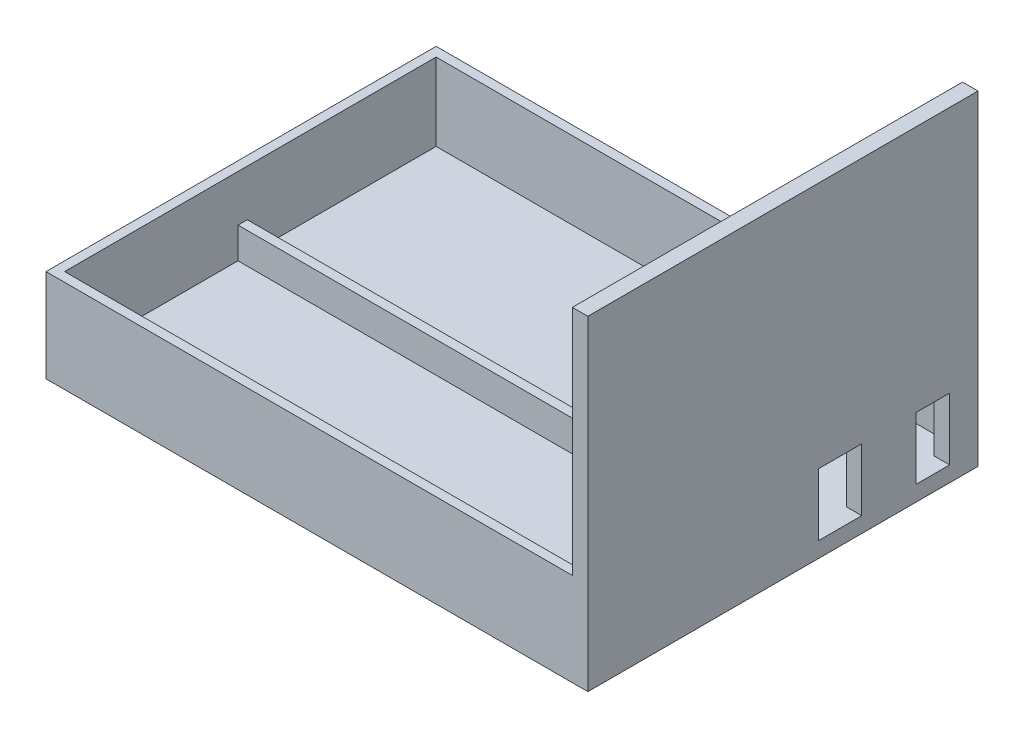
SolidWorks part; units mm, degrees
ref_plane "Płaszczyzna przednia" through (0, 0, 0) normal (0, 0, 1) x (1, 0, 0)
ref_plane "Płaszczyzna górna" through (0, 0, 0) normal (0, 1, 0) x (1, 0, 0)
ref_plane "Płaszczyzna prawa" through (0, 0, 0) normal (1, 0, 0) x (0, 0, -1)
sketch "Szkic1" plane through (0, 0, 0) normal (0, 1, 0) x (1, 0, 0)
  line L1 (-87.5, 63) -> (87.5, 63)
  line L2 (-87.5, 63) -> (-87.5, -63)
  line L3 (-87.5, -63) -> (87.5, -63)
  line L4 (87.5, 63) -> (87.5, -63)
  line L5 (-87.5, 63) -> (87.5, -63) construction
  line L6 (-87.5, -63) -> (87.5, 63) construction
  point P0 (0, 0)
  dimension "D1" = 175
  dimension "D2" = 126
extrude "Dodanie-wyciągnięcie1" add sketch "Szkic1" along normal blind 5
sketch "Szkic2" plane through (0, 5, 0) normal (0, 1, 0) x (1, 0, 0)
  line L0 (-87.5, -63) -> (87.5, -63) construction
  line L1 (-87.5, 63) -> (-84.5, 63)
  line L2 (-87.5, 63) -> (-87.5, -63)
  line L3 (-87.5, -63) -> (-84.5, -63)
  line L4 (-84.5, 63) -> (-84.5, -63)
  dimension "D1" = 3
extrude "Dodanie-wyciągnięcie2" add sketch "Szkic2" along normal blind 25
sketch "Szkic3" plane through (0, 5, 0) normal (0, 1, 0) x (1, 0, 0)
  line L0 (-84.5, -63) -> (87.5, -63) construction
  line L1 (87.5, 63) -> (82.5, 63)
  line L2 (87.5, 63) -> (87.5, -63)
  line L3 (87.5, -63) -> (82.5, -63)
  line L4 (82.5, 63) -> (82.5, -63)
  dimension "D1" = 5
extrude "Dodanie-wyciągnięcie3" add sketch "Szkic3" along normal blind 100
sketch "Szkic4" plane through (0, 5, 0) normal (0, 1, 0) x (1, 0, 0)
  line L0 (82.5, 63) -> (82.5, -63) construction
  line L1 (-84.5, -63) -> (82.5, -63)
  line L2 (-84.5, -63) -> (-84.5, -60)
  line L3 (-84.5, -60) -> (82.5, -60)
  line L4 (82.5, -63) -> (82.5, -60)
  dimension "D1" = 3
extrude "Dodanie-wyciągnięcie4" add sketch "Szkic4" along normal blind 25
sketch "Szkic5" plane through (0, 5, 0) normal (0, 1, 0) x (1, 0, 0)
  line L0 (82.5, 63) -> (82.5, -60) construction
  line L1 (-84.5, 63) -> (82.5, 63)
  line L2 (-84.5, 63) -> (-84.5, 60)
  line L3 (-84.5, 60) -> (82.5, 60)
  line L4 (82.5, 63) -> (82.5, 60)
  dimension "D1" = 3
extrude "Dodanie-wyciągnięcie5" add sketch "Szkic5" along normal blind 25
sketch "Szkic7" plane through (87.5, 0, 0) normal (1, 0, 0) x (0, 0, -1)
  line L1 (25.45, 25.1) -> (11.45, 25.1)
  line L2 (25.45, 25.1) -> (25.45, 5)
  line L3 (25.45, 5) -> (11.45, 5)
  line L4 (11.45, 25.1) -> (11.45, 5)
  line L7 (12.95, 20.1) -> (23.95, 20.1) construction
  line L8 (24.45, 19.6) -> (24.45, 10.1) construction
  line L9 (12.45, 10.1) -> (12.45, 19.6) construction
  line L10 (60, 5) -> (-60, 5) construction
  dimension "D1" = 5
  dimension "D2" = 0
  dimension "D3" = 1
  dimension "D4" = 1
extrude "Wytnij-wyciągnięcie1" cut sketch "Szkic7" against normal up to next
sketch "Szkic8" plane through (87.5, 0, 0) normal (1, 0, 0) x (0, 0, -1)
  line L0 (60, 5) -> (25.45, 5) construction
  line L1 (42.95, 25.1) -> (53.85, 25.1)
  line L2 (42.95, 25.1) -> (42.95, 5)
  line L3 (42.95, 5) -> (53.85, 5)
  line L4 (53.85, 25.1) -> (53.85, 5)
  line L5 (43.95, 10) -> (43.95, 20.1) construction
  line L6 (52.85, 20.1) -> (52.85, 10) construction
  line L7 (43.95, 20.1) -> (52.85, 20.1) construction
  dimension "D1" = 0
  dimension "D2" = 1
  dimension "D3" = 1
  dimension "D4" = 5
extrude "Wytnij-wyciągnięcie2" cut sketch "Szkic8" against normal up to next
sketch "Szkic10" plane through (0, 5, 0) normal (0, 1, 0) x (1, 0, 0)
  line L0 (82.5, 11.45) -> (82.5, -60) construction
  line L1 (82.5, -4) -> (-84.5, -4)
  line L2 (82.5, -4) -> (82.5, -1)
  line L3 (82.5, -1) -> (-84.5, -1)
  line L4 (-84.5, -4) -> (-84.5, -1)
  line L5 (-84.5, -60) -> (-84.5, 60) construction
  line L6 (82.5, -60) -> (-84.5, -60) construction
  dimension "D1" = 56
  dimension "D2" = 3
extrude "Dodanie-wyciągnięcie6" add sketch "Szkic10" along normal blind 10
